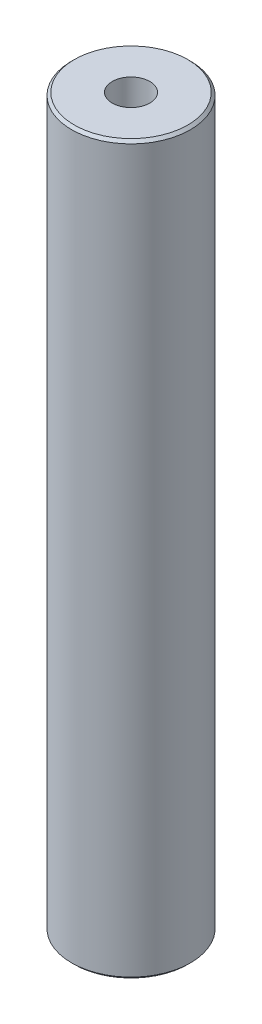
SolidWorks part; units mm, degrees
ref_plane "Front Plane" through (0, 0, 0) normal (0, 0, 1) x (1, 0, 0)
ref_plane "Top Plane" through (0, 0, 0) normal (0, 1, 0) x (1, 0, 0)
ref_plane "Right Plane" through (0, 0, 0) normal (1, 0, 0) x (0, 0, -1)
sketch "Sketch1" plane through (0, 0, 0) normal (0, 1, 0) x (1, 0, 0)
  circle A0 centre (0, 0) radius 20
  dimension "SHAFT_OD" = 40
extrude "Boss-Extrude1" add sketch "Sketch1" along normal blind 244.582
sketch "Sketch2" plane through (0, 0, 0) normal (0, 1, 0) x (1, 0, 0)
  circle A0 centre (0, 0) radius 6.3152
  dimension "BORE_D" = 12.6305
extrude "Cut-Extrude1" cut sketch "Sketch2" along normal through all
chamfer "Chamfer1" distance 0.9071 angle 45 2 edges at (0, 244.582, 20) (0, 0, 20)
